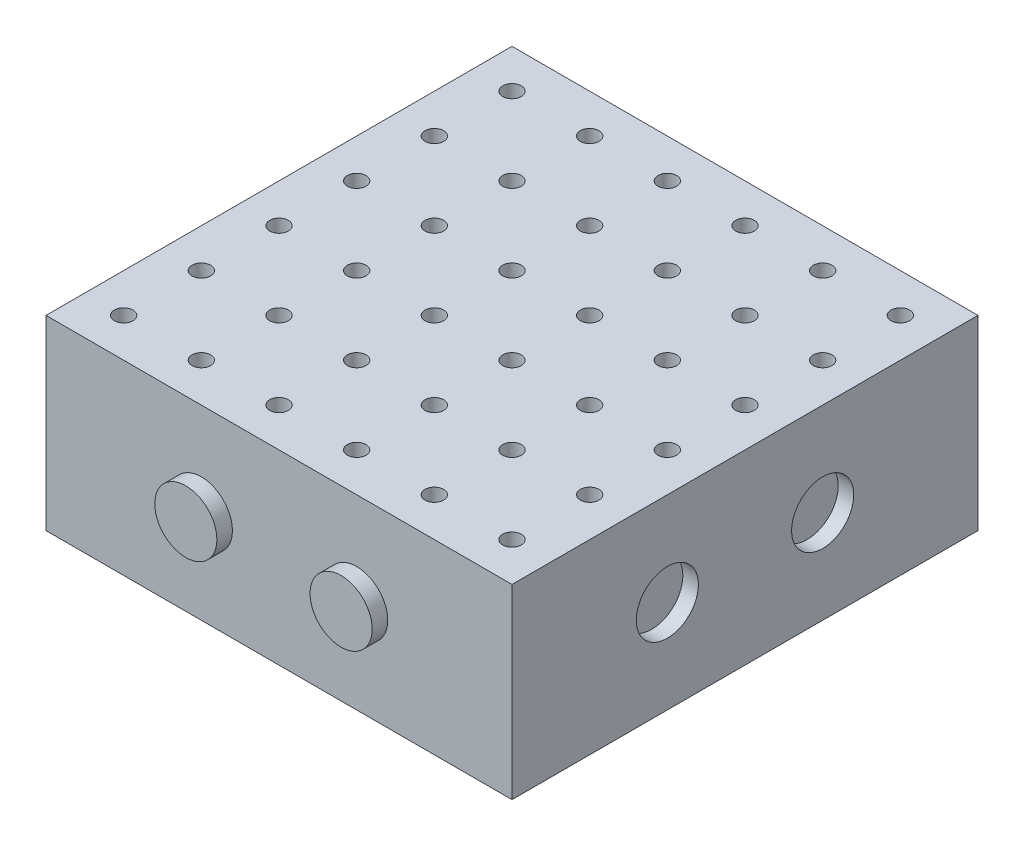
SolidWorks part; units mm, degrees
ref_plane "Front Plane" through (0, 0, 0) normal (0, 0, 1) x (1, 0, 0)
ref_plane "Top Plane" through (0, 0, 0) normal (0, 1, 0) x (1, 0, 0)
ref_plane "Right Plane" through (0, 0, 0) normal (1, 0, 0) x (0, 0, -1)
sketch "Sketch1" plane through (0, 0, 0) normal (0, 1, 0) x (1, 0, 0)
  line L1 (-55.9774, 107.8352) -> (94.0226, 107.8352)
  line L2 (-55.9774, 107.8352) -> (-55.9774, -42.1648)
  line L3 (-55.9774, -42.1648) -> (94.0226, -42.1648)
  line L4 (94.0226, 107.8352) -> (94.0226, -42.1648)
  circle A0 centre (-43.4774, 95.3352) radius 3
  circle A1 centre (-18.4774, 95.3352) radius 3
  circle A2 centre (6.5226, 95.3352) radius 3
  circle A3 centre (31.5226, 95.3352) radius 3
  circle A4 centre (56.5226, 95.3352) radius 3
  circle A5 centre (81.5226, 95.3352) radius 3
  circle A6 centre (-18.4774, 70.3352) radius 3
  circle A7 centre (6.5226, 70.3352) radius 3
  circle A8 centre (31.5226, 70.3352) radius 3
  circle A9 centre (56.5226, 70.3352) radius 3
  circle A10 centre (81.5226, 70.3352) radius 3
  circle A11 centre (-18.4774, 45.3352) radius 3
  circle A12 centre (6.5226, 45.3352) radius 3
  circle A13 centre (31.5226, 45.3352) radius 3
  circle A14 centre (56.5226, 45.3352) radius 3
  circle A15 centre (81.5226, 45.3352) radius 3
  circle A16 centre (-18.4774, 20.3352) radius 3
  circle A17 centre (6.5226, 20.3352) radius 3
  circle A18 centre (31.5226, 20.3352) radius 3
  circle A19 centre (56.5226, 20.3352) radius 3
  circle A20 centre (81.5226, 20.3352) radius 3
  circle A21 centre (-18.4774, -4.6648) radius 3
  circle A22 centre (6.5226, -4.6648) radius 3
  circle A23 centre (31.5226, -4.6648) radius 3
  circle A24 centre (56.5226, -4.6648) radius 3
  circle A25 centre (81.5226, -4.6648) radius 3
  circle A26 centre (-18.4774, -29.6648) radius 3
  circle A27 centre (6.5226, -29.6648) radius 3
  circle A28 centre (31.5226, -29.6648) radius 3
  circle A29 centre (56.5226, -29.6648) radius 3
  circle A30 centre (81.5226, -29.6648) radius 3
  circle A31 centre (-43.4774, 70.3352) radius 3
  circle A32 centre (-43.4774, 45.3352) radius 3
  circle A33 centre (-43.4774, 20.3352) radius 3
  circle A34 centre (-43.4774, -4.6648) radius 3
  circle A35 centre (-43.4774, -29.6648) radius 3
  dimension "D1" = 6
  dimension "D2" = 12.5
  dimension "D5" = 12.5
  dimension "D3" = 6
  dimension "D4" = 6
extrude "Boss-Extrude1" add sketch "Sketch1" along normal blind 60
sketch "Sketch4" plane through (94.0226, 0, 0) normal (1, 0, 0) x (0, 0, -1)
  line L1 (-42.1648, 60) -> (-42.1648, 0) construction
  line L4 (-42.1648, 60) -> (107.8352, 60) construction
  line L5 (107.8352, 60) -> (107.8352, 0) construction
  circle A0 centre (7.8352, 30) radius 10
  circle A3 centre (57.8352, 30) radius 10
  dimension "D3" = 50
  dimension "D5" = 20
  dimension "D6" = 20
  dimension "D1" = 50
  dimension "D2" = 30
  dimension "D4" = 30
extrude "Boss-Extrude3" add sketch "Sketch4" against normal blind 8 contours A3
extrude "Cut-Extrude1" cut sketch "Sketch4<6>" against normal blind 5
sketch "Sketch4<6>" plane through (94.0226, 0, 0) normal (1, 0, 0) x (0, 0, -1) same geometry as "Sketch4"
sketch "Sketch5" plane through (0, 0, -107.8352) normal (0, 0, -1) x (-1, 0, 0)
  line L0 (-94.0226, 60) -> (-94.0226, 0) construction
  line L1 (-94.0226, 0) -> (55.9774, 0) construction
  line L2 (55.9774, 60) -> (55.9774, 0) construction
  circle A0 centre (-44.0226, 30) radius 10
  circle A1 centre (5.9774, 30) radius 10
  dimension "D1" = 20
  dimension "D2" = 20
  dimension "D3" = 50
  dimension "D4" = 30
  dimension "D5" = 50
  dimension "D6" = 30
extrude "Cut-Extrude2" cut sketch "Sketch5" against normal blind 5
sketch "Sketch6" plane through (-55.9774, 0, 0) normal (-1, 0, 0) x (0, 0, 1)
  line L0 (-107.8352, 60) -> (-107.8352, 0) construction
  line L1 (42.1648, 60) -> (42.1648, 0) construction
  line L2 (-107.8352, 0) -> (42.1648, 0) construction
  circle A0 centre (-57.8352, 30) radius 10
  circle A1 centre (-7.8352, 30) radius 10
  dimension "D1" = 20
  dimension "D2" = 20
  dimension "D3" = 50
  dimension "D4" = 50
  dimension "D5" = 30
  dimension "D6" = 30
extrude "Boss-Extrude4" add sketch "Sketch6" along normal blind 5
sketch "Sketch7" plane through (0, 0, 42.1648) normal (0, 0, 1) x (1, 0, 0)
  line L0 (-55.9774, 0) -> (94.0226, 0) construction
  line L1 (-55.9774, 60) -> (-55.9774, 0) construction
  line L2 (94.0226, 60) -> (94.0226, 0) construction
  circle A0 centre (-5.9774, 30) radius 10
  circle A1 centre (44.0226, 30) radius 10
  dimension "D1" = 20
  dimension "D2" = 20
  dimension "D3" = 30
  dimension "D4" = 30
  dimension "D5" = 50
  dimension "D6" = 50
extrude "Boss-Extrude5" add sketch "Sketch7" along normal blind 5
sketch "Sketch8" plane through (0, 0, 0) normal (0, -1, 0) x (1, 0, 0)
  line L0 (-55.9774, 42.1648) -> (94.0226, 42.1648) construction
  line L1 (-41.9774, 38.1648) -> (80.0226, 38.1648)
  line L2 (-51.9774, 28.1648) -> (-51.9774, -93.8352)
  line L3 (-41.9774, -103.8352) -> (80.0226, -103.8352)
  line L4 (90.0226, 28.1648) -> (90.0226, -93.8352)
  line L5 (94.0226, 42.1648) -> (94.0226, -107.8352) construction
  line L6 (94.0226, -107.8352) -> (-55.9774, -107.8352) construction
  line L7 (-55.9774, -107.8352) -> (-55.9774, 42.1648) construction
  arc A0 (-51.9774, -93.8352) -> (-41.9774, -103.8352) centre (-41.9774, -93.8352) ccw
  arc A1 (80.0226, -103.8352) -> (90.0226, -93.8352) centre (80.0226, -93.8352) ccw
  arc A2 (80.0226, 38.1648) -> (90.0226, 28.1648) centre (80.0226, 28.1648) cw
  arc A3 (-41.9774, 38.1648) -> (-51.9774, 28.1648) centre (-41.9774, 28.1648) ccw
  dimension "D5" = 10
  dimension "D1" = 4
  dimension "D2" = 4
  dimension "D3" = 4
  dimension "D4" = 4
extrude "Cut-Extrude3" cut sketch "Sketch8" against normal blind 15
